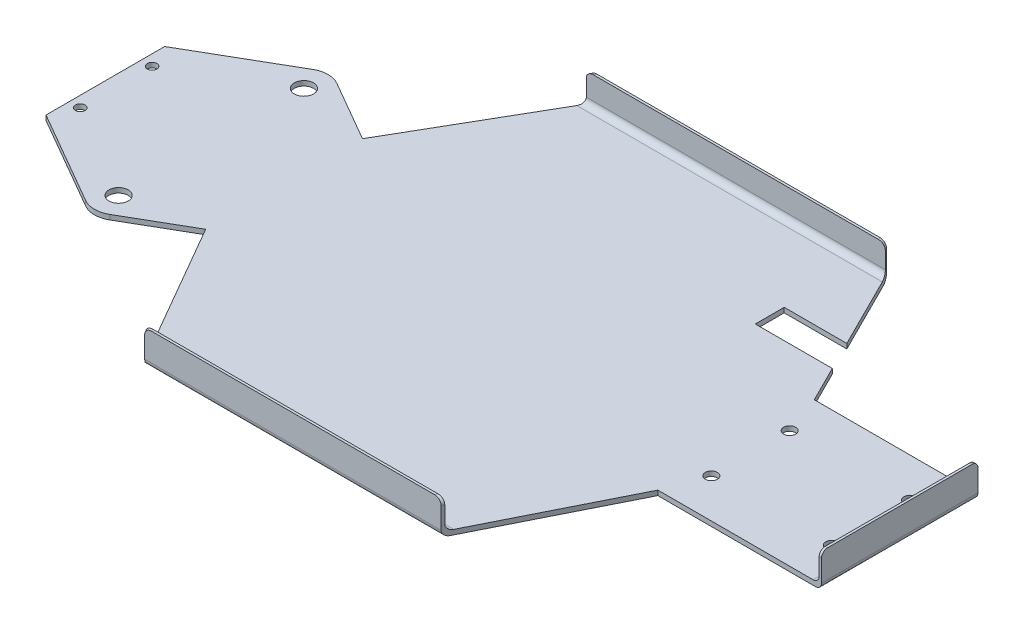
SolidWorks part; units mm, degrees
ref_plane "Front Plane" through (0, 0, 0) normal (0, 0, 1) x (1, 0, 0)
ref_plane "Top Plane" through (0, 0, 0) normal (0, 1, 0) x (1, 0, 0)
ref_plane "Right Plane" through (0, 0, 0) normal (1, 0, 0) x (0, 0, -1)
sketch "Sketch1" plane through (0, 0, 0) normal (0, 1, 0) x (1, 0, 0)
  line L0 (165, 32.5) -> (97, 32.5)
  line L1 (-89.8231, -92.5) -> (67, -92.5)
  line L3 (-56.1347, 92.5) -> (67, 92.5)
  line L4 (165, -32.5) -> (165, 32.5)
  line L5 (-165, -92.5) -> (165, 92.5) construction
  line L6 (-165, 92.5) -> (165, -92.5) construction
  line L7 (97, 32.5) -> (89.5, 47.5)
  line L8 (-187.8754, 0) -> (194.9929, 0) construction
  line L9 (165, -32.5) -> (97, -32.5)
  line L10 (97, -32.5) -> (67, -92.5)
  line L11 (165, 92.5) -> (165, 32.5) construction
  line L12 (67, 92.5) -> (165, 92.5) construction
  line L13 (67, -92.5) -> (165, -92.5) construction
  line L14 (165, -32.5) -> (165, -92.5) construction
  line L16 (103, -16.25) -> (153, -16.25) construction
  line L17 (103, -16.25) -> (103, 16.25) construction
  line L18 (103, 16.25) -> (153, 16.25) construction
  line L19 (153, -16.25) -> (153, 16.25) construction
  line L20 (103, -16.25) -> (153, 16.25) construction
  line L21 (103, 16.25) -> (153, -16.25) construction
  line L25 (-121, -38.5) -> (-89.8231, -92.5) construction
  line L26 (-56.1347, -92.5) -> (-90.7337, -32.5728)
  line L27 (-90.7337, -32.5728) -> (-116, -47.1603)
  line L28 (-121, 38.5) -> (-121, -38.5) construction
  line L29 (-126, -47.1603) -> (-165, -24.6436)
  line L30 (-90.7337, 32.5728) -> (-116, 47.1603)
  line L31 (-56.1347, 92.5) -> (-90.7337, 32.5728)
  line L32 (-165, -24.6436) -> (-165, 24.6436)
  line L33 (-89.8231, -92.5) -> (-165, -92.5) construction
  line L34 (-165, -92.5) -> (-165, 92.5) construction
  line L35 (-165, 92.5) -> (-56.1347, 92.5) construction
  line L36 (-165, 24.6436) -> (-126, 47.1603)
  line L37 (57.5, 47.5) -> (57.5, 59.5)
  line L38 (57.5, 59.5) -> (83.5, 59.5)
  line L39 (57.5, 47.5) -> (89.5, 47.5)
  line L40 (83.5, 59.5) -> (67, 92.5)
  line L41 (-121, 184.5763) -> (-121, -179.129) construction
  circle A0 centre (-121, 38.5) radius 4
  circle A1 centre (-121, -38.5) radius 4
  circle A2 centre (103, 16.25) radius 2.5
  circle A3 centre (153, 16.25) radius 2.5
  circle A4 centre (103, -16.25) radius 2.5
  circle A5 centre (153, -16.25) radius 2.5
  arc A6 (-126, -47.1603) -> (-116, -47.1603) centre (-121, -38.5) ccw
  arc A7 (-126, 47.1603) -> (-116, 47.1603) centre (-121, 38.5) cw
  circle A8 centre (-121, 0) radius 22.9289 construction
  circle A9 centre (-160.4976, 14.92) radius 2
  circle A10 centre (-160.4976, 14.92) radius 2 construction
  circle A11 centre (-160.4976, -14.92) radius 2
  circle A12 centre (-160.4976, -14.92) radius 2 construction
  point P0 (0, 0)
  point P18 (128, 0)
  dimension "D5" = 8
  dimension "D12" = 5
  dimension "D13" = 5
  dimension "D14" = 5
  dimension "D15" = 5
  dimension "D21" = 10
  dimension "D2" = 185
  dimension "D3" = 65
  dimension "D4" = 30
  dimension "D6" = 330
  dimension "D7" = 54
  dimension "D8" = 68
  dimension "D9" = 32.5
  dimension "D10" = 50
  dimension "D11" = 12
  dimension "D16" = 15
  dimension "D19" = 60
  dimension "D20" = 29.175
  dimension "D22" = 44
  dimension "D23" = 60
  dimension "D24" = 60
  dimension "D25" = 32
  dimension "D27" = 12
extrude "Boss-Extrude1" add sketch "Sketch1" along normal blind 2 contours A7 A6 L27 L26 L1 L10 L9 L4 L0 L7 L3 L31 L30 A5 A4 A3 A2 A0 A1 region at (-1.2674, 0, 0.4579)
sketch "Sketch2" plane through (0, 2, 0) normal (0, 1, 0) x (1, 0, 0)
  line L0 (-56.1347, -92.5) -> (67, -92.5)
  line L1 (67, -92.5) -> (67.5, -91.5)
  line L2 (97, -32.5) -> (67, -92.5) construction
  line L3 (67.5, -91.5) -> (-56.712, -91.5)
  line L4 (-56.1347, -92.5) -> (-90.7337, -32.5728) construction
  line L5 (-56.712, -91.5) -> (-56.1347, -92.5)
  line L6 (-56.1347, 92.5) -> (67, 92.5)
  line L7 (67, 92.5) -> (67.5, 91.5)
  line L8 (83.5, 59.5) -> (67, 92.5) construction
  line L9 (67.5, 91.5) -> (-56.712, 91.5)
  line L10 (-56.1347, 92.5) -> (-90.7337, 32.5728) construction
  line L11 (-56.712, 91.5) -> (-56.1347, 92.5)
  line L16 (165, 32.5) -> (97, 32.5) construction
  line L17 (165, -32.5) -> (164, -32.5)
  line L18 (165, -32.5) -> (165, 32.5)
  line L19 (165, 32.5) -> (164, 32.5)
  line L20 (164, -32.5) -> (164, 32.5)
  dimension "D1" = 1
  dimension "D2" = 1
  dimension "D3" = 1
extrude "Boss-Extrude2" add sketch "Sketch2" along normal blind 12
fillet "Fillet1" radius 2.5 12 edges at (67.25, 14, 92) (-56.4234, 14, 92) (-56.4234, 14, -92) (67.25, 14, -92) (5.394, 2, 91.5) (5.4327, 0, 92.5) (5.4327, 0, -92.5) (5.394, 2, -91.5) (164.5, 14, -32.5) (164, 2, 0) (164.5, 14, 32.5) (165, 0, 0)
